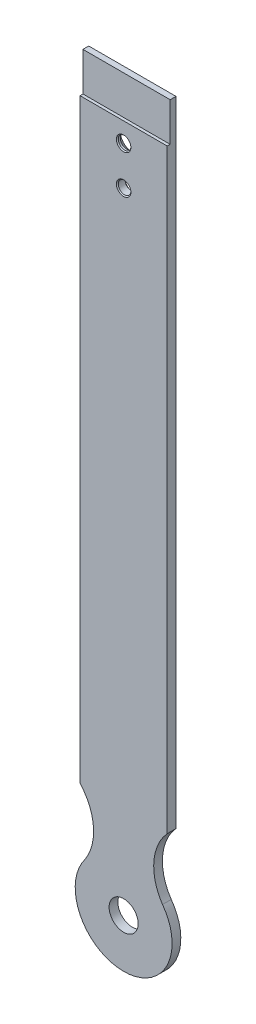
SolidWorks part; units mm, degrees
ref_plane "Спереди" through (0, 0, 0) normal (0, 0, 1) x (1, 0, 0)
ref_plane "Сверху" through (0, 0, 0) normal (0, 1, 0) x (1, 0, 0)
ref_plane "Справа" through (0, 0, 0) normal (1, 0, 0) x (0, 0, -1)
sketch "Эскиз1" plane through (0, 0, 0) normal (0, 0, 1) x (1, 0, 0)
  line L0 (22.5, 72.8118) -> (22.5, 400)
  line L1 (22.5, 400) -> (-22.5, 400)
  line L2 (0, 481.0809) -> (0, -73.6647) construction
  line L3 (-22.5, 72.8118) -> (-22.5, 400)
  arc A0 (-20.0599, 39.9199) -> (20.0599, 39.9199) centre (0, 25) ccw
  arc A1 (20.0599, 39.9199) -> (22.5, 72.8118) centre (42.1304, 54.819) cw
  arc A2 (-20.0599, 39.9199) -> (-22.5, 72.8118) centre (-42.1304, 54.819) ccw
  circle A3 centre (0, 370) radius 3.25
  circle A4 centre (0, 350) radius 3.25
  circle A5 centre (0, 25) radius 7.5
  point P13 (0, 400)
  point P15 (0, 0)
  point P17 (0, 0)
  point P18 (0, 0)
  point P19 (0, 0)
  point P20 (0, 0)
  point P21 (0, 0)
extrude "Бобышка-Вытянуть1" add sketch "Эскиз1" along normal blind 4.5
sketch "Эскиз2" plane through (-22.5, 0, 0) normal (-1, 0, 0) x (0, 0, 1)
  line L0 (3, 400) -> (3, 380.0564)
  line L1 (4.5, 400) -> (0, 400) construction
  line L2 (3, 380.0564) -> (4.5, 380.0564)
  line L3 (4.5, 400) -> (4.5, 72.8118) construction
  line L4 (4.5, 380.0564) -> (4.5, 400)
  line L5 (4.5, 400) -> (3, 400)
extrude "Вырез-Вытянуть1" cut sketch "Эскиз2" against normal through all
chamfer "Фаска1" distance 3 angle 45 1 edges at (3.25, 370, 0)
chamfer "Фаска2" distance 0.5 angle 45 3 edges at (3.25, 350, 0) (3.25, 350, 4.5) (3.25, 370, 4.5)
